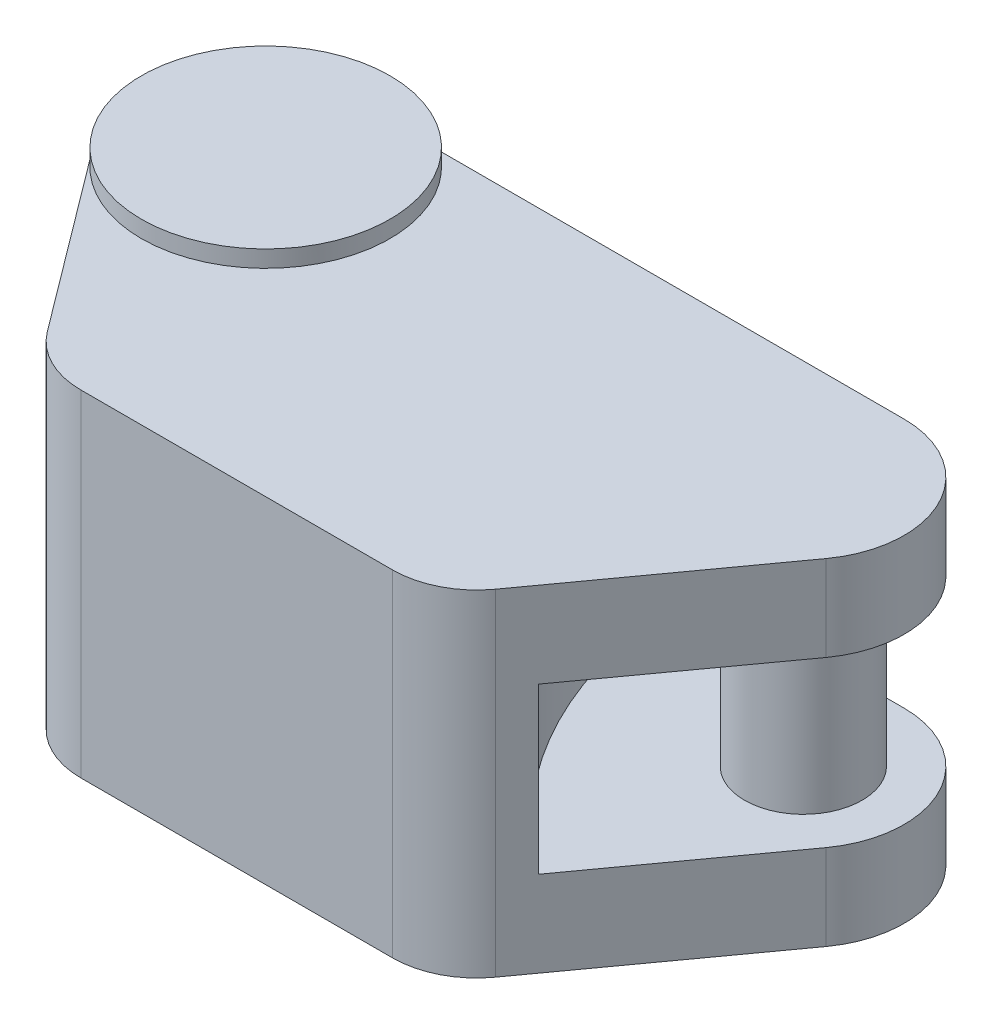
SolidWorks part; units mm, degrees
ref_plane "Front Plane" through (0, 0, 0) normal (0, 0, 1) x (1, 0, 0)
ref_plane "Top Plane" through (0, 0, 0) normal (0, 1, 0) x (1, 0, 0)
ref_plane "Right Plane" through (0, 0, 0) normal (1, 0, 0) x (0, 0, -1)
sketch "Sketch2" plane through (0, 0, 0) normal (0, 1, 0) x (0, 0, -1)
  line L0 (-107.95, -38.1) -> (-107.95, -155.921)
  line L1 (0, 0) -> (0, -203.2) construction
  line L5 (-94.8077, -181.6468) -> (-22.3292, -234.071)
  line L6 (38.1, -203.2) -> (38.1, -27.5036)
  line L8 (-95.25, -12.7) -> (-28.194, 37.592)
  arc A15 (38.1, -27.5036) -> (-28.194, 37.592) centre (0, 0) ccw
  arc A16 (-22.3292, -234.071) -> (38.1, -203.2) centre (0, -203.2) ccw
  arc A17 (-95.25, -12.7) -> (-107.95, -38.1) centre (-76.2, -38.1) ccw
  arc A18 (-107.95, -155.921) -> (-94.8077, -181.6468) centre (-76.2, -155.921) ccw
  dimension "D1" = 76.2
  dimension "D2" = 203.2
  dimension "D5" = 93.98
  dimension "D8" = 155.921
  dimension "D3" = 38.1
  dimension "D4" = 31.75
  dimension "D6" = 31.75
  dimension "D7" = 76.2
extrude "Boss-Extrude2" add sketch "Sketch2" along normal blind 63.5 and the other way blind 63.5
sketch "Sketch3" plane through (0, 63.5, 0) normal (0, 1, 0) x (1, 0, 0)
  circle A0 centre (0, 0) radius 46.99
extrude "Boss-Extrude3" add sketch "Sketch3" along normal blind 6.35
sketch "Sketch4" plane through (0, 0, 0) normal (0, 1, 0) x (1, 0, 0)
  line L0 (125.3798, 38.1) -> (277.7798, 38.1)
  line L1 (181.6468, -94.8077) -> (234.071, -22.3292) construction
  line L2 (277.7798, 38.1) -> (188.4631, -85.3839)
  arc A0 (188.4631, -85.3839) -> (125.3798, 38.1) centre (277.7798, 38.1) cw
extrude "Cut-Extrude1" cut sketch "Sketch4" against normal blind 31.115 and the other way blind 31.115
sketch "Sketch5" plane through (0, 0, 0) normal (0, 1, 0) x (1, 0, 0)
  circle A0 centre (203.2, 0) radius 22.225
  dimension "D1" = 44.45
extrude "Boss-Extrude4" add sketch "Sketch5" along normal blind 31.115 and the other way blind 31.115
ref_axis "Axis1" through (0, -63.5, 0) along (0, 1, 0)
ref_point "Point1"
ref_axis "Axis2" through (203.2, -31.115, 0) along (0, 1, 0)
